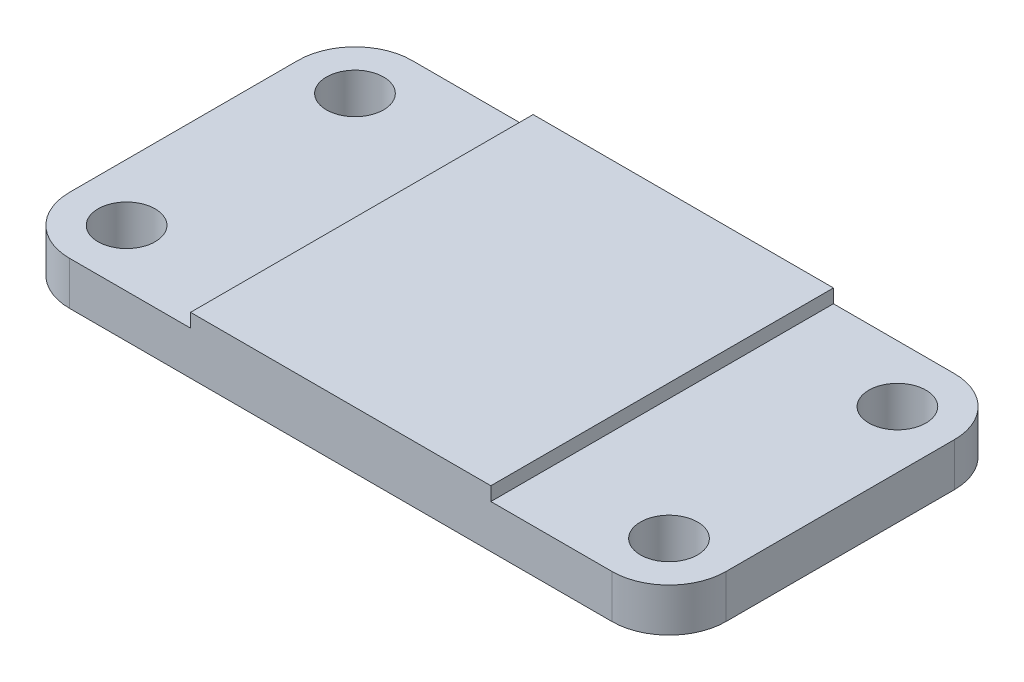
SolidWorks part; units mm, degrees
material "Nylon 101"
ref_plane "Front Plane" through (0, 0, 0) normal (0, 0, 1) x (1, 0, 0)
ref_plane "Top Plane" through (0, 0, 0) normal (0, 1, 0) x (1, 0, 0)
ref_plane "Right Plane" through (0, 0, 0) normal (1, 0, 0) x (0, 0, -1)
ref_axis "X-axis" through (-88.99, 0, 0) along (1, 0, 0)
ref_axis "Y-axis" through (0, 55, 0) along (0, -1, 0)
ref_axis "Z-axis" through (0, 0, -88.99) along (0, 0, 1)
sketch "Sketch1" plane through (0, 0, 0) normal (0, 1, 0) x (1, 0, 0)
  line L1 (-73.025, 38.1) -> (73.025, 38.1)
  line L2 (-73.025, 38.1) -> (-73.025, -38.1)
  line L3 (-73.025, -38.1) -> (73.025, -38.1)
  line L4 (73.025, 38.1) -> (73.025, -38.1)
  line L5 (-73.025, 38.1) -> (73.025, -38.1) construction
  line L6 (-73.025, -38.1) -> (73.025, 38.1) construction
  point P0 (0, 0)
  dimension "D1" = 76.2
  dimension "D2" = 146.05
extrude "Boss-Extrude1" add sketch "Sketch1" along normal blind 9.652
sketch "Sketch3" plane through (0, 9.652, 0) normal (0, 1, 0) x (1, 0, 0)
  line L0 (-73.025, -38.1) -> (73.025, -38.1) construction
  line L1 (-33.401, 38.1) -> (33.401, 38.1)
  line L2 (-33.401, 38.1) -> (-33.401, -38.1)
  line L3 (-33.401, -38.1) -> (33.401, -38.1)
  line L4 (33.401, 38.1) -> (33.401, -38.1)
  line L5 (-33.401, 38.1) -> (33.401, -38.1) construction
  line L6 (-33.401, -38.1) -> (33.401, 38.1) construction
  point P0 (0, 0)
  point P9 (0, -38.1)
  dimension "D1" = 66.802
extrude "Boss-Extrude2" add sketch "Sketch3" along normal blind 3.048
fillet "Fillet1" radius 12.7 4 edges at (73.025, 4.826, -38.1) (73.025, 4.826, 38.1) (-73.025, 4.826, 38.1) (-73.025, 4.826, -38.1)
hole_wizard "1/4 (0.5) Diameter Hole1" positions "Sketch7" profile "Sketch8" hole size "1/4" standard "ANSI Inch" end condition through all
sketch "Sketch7" plane through (0, 9.652, 0) normal (0, 1, 0) x (1, 0, 0)
  point P0 (-60.325, 25.4)
  point P3 (-60.325, -25.4)
  point P6 (60.325, -25.4)
  point P9 (60.325, 25.4)
sketch "Sketch8" plane through (-60.325, 9.652, -25.4) normal (1, 0, 0) x (0, 0, 1)
  line L0 (0, 0) -> (0, 9.652)
  line L1 (0, 9.652) -> (6.35, 9.652)
  line L2 (6.35, 9.652) -> (6.35, 0)
  line L5 (6.35, 0) -> (0, 0)
  line L11 (0, -6.35) -> (0, 107.95) construction
  dimension "Thru Hole Dia." = 12.7
  dimension "Thru Hole Depth" = 9.652
